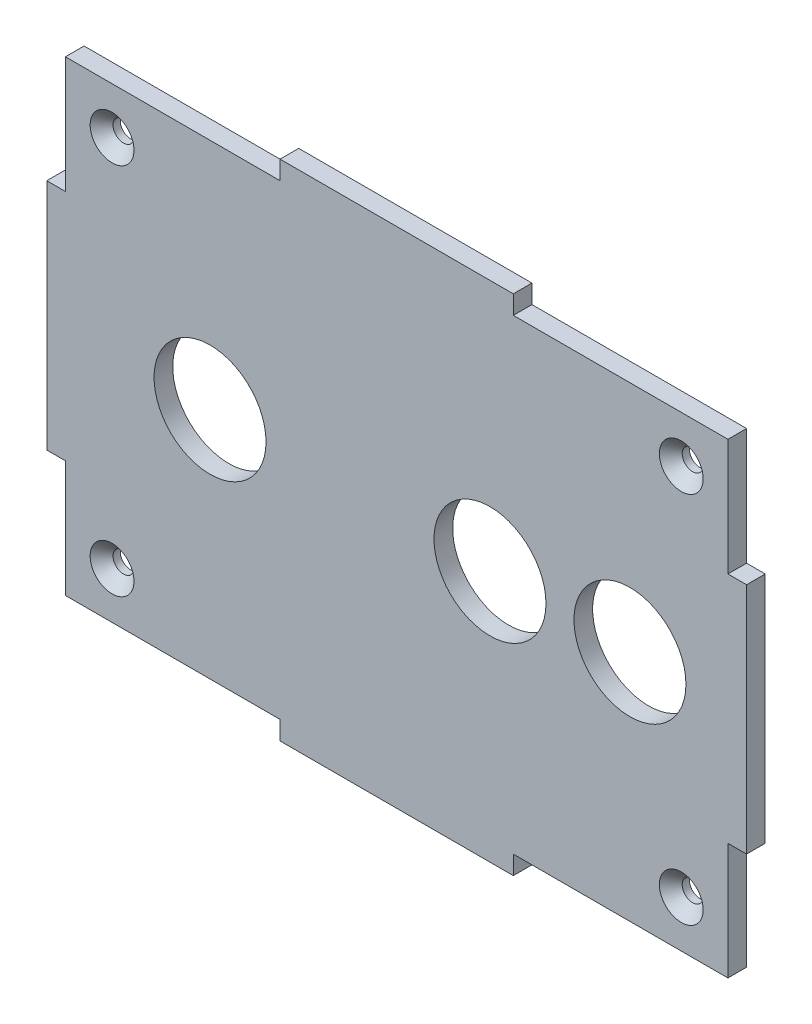
SolidWorks part; units mm, degrees
ref_plane "Front Plane" through (0, 0, 0) normal (0, 0, 1) x (1, 0, 0)
ref_plane "Top Plane" through (0, 0, 0) normal (0, 1, 0) x (1, 0, 0)
ref_plane "Right Plane" through (0, 0, 0) normal (1, 0, 0) x (0, 0, -1)
sketch "Sketch1" plane through (0, 0, 0) normal (0, 0, 1) x (1, 0, 0)
  line L0 (0, 54) -> (0, 0) construction
  line L1 (-71, -50) -> (71, -50)
  line L2 (-71, -50) -> (-71, 50)
  line L3 (-71, 50) -> (71, 50)
  line L4 (71, -50) -> (71, 50)
  line L5 (-71, -50) -> (71, 50) construction
  line L6 (-71, 50) -> (71, -50) construction
  line L7 (-71, 25) -> (-75, 25)
  line L8 (-71, 25) -> (-71, -25)
  line L9 (-71, -25) -> (-75, -25)
  line L10 (-75, 25) -> (-75, -25)
  line L11 (-25, 50) -> (25, 50)
  line L12 (-25, 50) -> (-25, 54)
  line L13 (-25, 54) -> (25, 54)
  line L14 (25, 50) -> (25, 54)
  line L15 (0, 0) -> (-75, 0) construction
  line L16 (25, -50) -> (25, -54)
  line L17 (-25, -50) -> (25, -50)
  line L18 (-25, -50) -> (-25, -54)
  line L19 (-25, -54) -> (25, -54)
  line L20 (71, -25) -> (75, -25)
  line L21 (75, 25) -> (75, -25)
  line L22 (71, 25) -> (75, 25)
  line L23 (71, 25) -> (71, -25)
  point P0 (0, 0)
  dimension "D1" = 142
  dimension "D2" = 100
  dimension "D3" = 4
  dimension "D4" = 4
  dimension "D5" = 50
  dimension "D6" = 50
extrude "Boss-Extrude2" add sketch "Sketch1" along normal blind 4 contours L1 L4 L3 L2 | L3 L14 L13 L12 | L22 L4 L20 L21 | L7 L10 L9 L2 | L19 L16 L17 L18 region at (0, 0, 0) region at (-73, 0, 0) region at (73, 0, 0) region at (0, 52, 0)
sketch "Sketch2" plane through (0, 0, 4) normal (0, 0, 1) x (1, 0, 0)
  line L0 (-40, 0) -> (0, 0)
  line L1 (0, 0) -> (20, 0)
  line L2 (20, 0) -> (50, 0)
  circle A0 centre (-40, 0) radius 12
  circle A1 centre (20, 0) radius 12
  circle A2 centre (50, 0) radius 12
  dimension "D1" = 24
  dimension "D2" = 40
  dimension "D3" = 20
  dimension "D4" = 30
extrude "Cut-Extrude1" cut sketch "Sketch2" against normal up to next contours L1 A1 L2 | L2 A1 L1 | A2 | A0 region at (50, 11.6606, 4) region at (20, 5.093, 4) region at (20, -5.093, 4) region at (-51.6606, 0, 4)
sketch "Sketch3" plane through (0, 0, 4) normal (0, 0, 1) x (1, 0, 0)
  line L0 (-71, 50) -> (-25, 50) construction
  line L1 (-61, 40) -> (61, 40)
  line L2 (-61, 40) -> (-61, -40)
  line L3 (-61, -40) -> (61, -40)
  line L4 (61, 40) -> (61, -40)
  line L5 (-71, 25) -> (-71, 50) construction
  line L6 (71, 25) -> (71, 50) construction
  line L7 (25, -50) -> (71, -50) construction
  point P12 (0, 0)
  dimension "D1" = 10
  dimension "D2" = 10
  dimension "D3" = 10
  dimension "D4" = 10
hole_wizard "CSK for M4 Countersunk Flat Head Screw1" positions "3DSketch1" profile "Sketch4" countersink size "M4" standard "ISO" end condition up to next
sketch3d "3DSketch1"
  point P0 (-61, 40, 4)
  point P3 (61, 40, 4)
  point P6 (61, -40, 4)
  point P9 (-61, -40, 4)
sketch "Sketch4" plane through (-61, 40, 4) normal (1, 0, 0) x (0, -1, 0)
  line L0 (0, 0) -> (0, 4)
  line L1 (0, 4) -> (2.25, 4)
  line L2 (2.25, 4) -> (2.25, 2.45)
  line L3 (2.25, 2.45) -> (4.7, 0)
  line L5 (4.7, 0) -> (0, 0)
  line L6 (-2.25, 2.45) -> (-4.7, 0) construction
  line L11 (0, -6.35) -> (0, 107.95) construction
  dimension "Thru Hole Dia." = 4.5
  dimension "Thru Hole Depth" = 4
  dimension "Near C'Sink Dia." = 9.4
  dimension "Near C'Sink Angle" = 90
